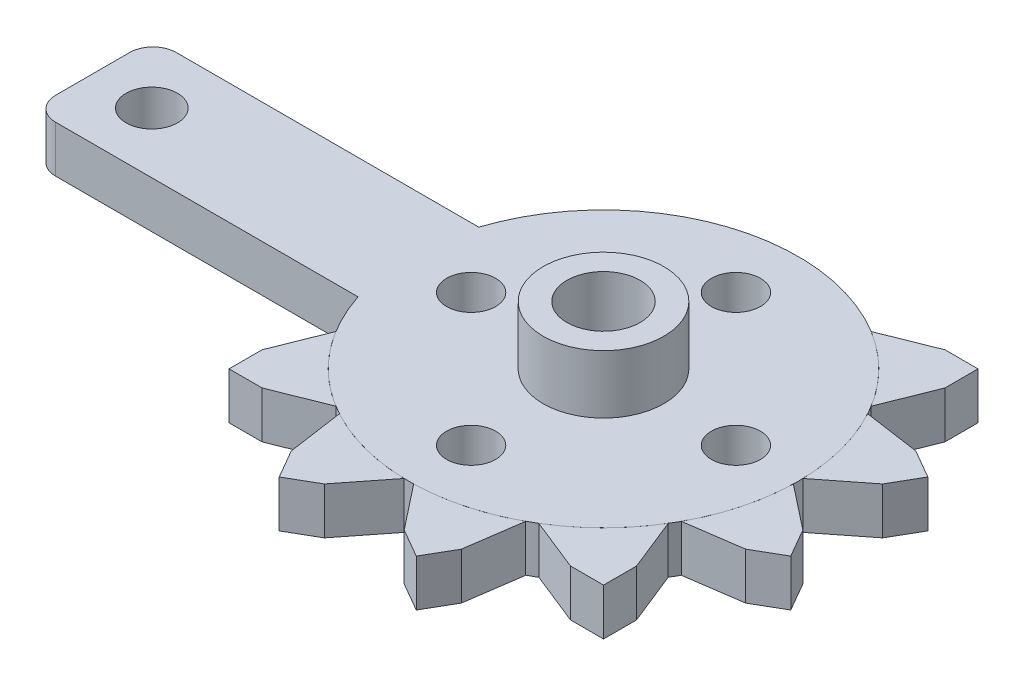
SolidWorks part; units mm, degrees
note: The reader was unsure of these and kept them because the rebuilt part matched: shared geometry of "Sketch1<3>".
ref_plane "Front Plane" through (0, 0, 0) normal (0, 0, 1) x (1, 0, 0)
ref_plane "Top Plane" through (0, 0, 0) normal (0, 1, 0) x (1, 0, 0)
ref_plane "Right Plane" through (0, 0, 0) normal (1, 0, 0) x (0, 0, -1)
sketch "Sketch1" plane through (0, 0, 0) normal (0, 1, 0) x (1, 0, 0)
  line L0 (-3.875, 0) -> (-3.875, 12.8)
  line L1 (-3.875, 12.8) -> (3.875, 12.8)
  line L2 (3.875, 12.8) -> (3.875, 0)
  line L3 (0, 0) -> (0, 8.5)
  line L4 (0, 3.875) -> (12.8, 3.875)
  line L5 (12.8, 3.875) -> (12.8, -3.875)
  line L6 (12.8, -3.875) -> (0, -3.875)
  line L7 (3.875, 0) -> (3.875, -12.8)
  line L8 (3.875, -12.8) -> (-3.875, -12.8)
  line L9 (-3.875, -12.8) -> (-3.875, 0)
  line L10 (0, -3.875) -> (-12.8, -3.875)
  line L11 (-12.8, -3.875) -> (-12.8, 3.875)
  line L12 (-12.8, 3.875) -> (0, 3.875)
  line L13 (-12.8, -3.875) -> (-32.8, -3.875)
  line L14 (-32.8, -3.875) -> (-32.8, 3.875)
  line L15 (-32.8, 3.875) -> (-12.8, 3.875)
  line L16 (0, 0) -> (-29, 0)
  circle A0 centre (0, 0) radius 2.35
  circle A1 centre (0, 0) radius 5.25
  circle A2 centre (0, 0) radius 3.875
  circle A3 centre (0, 8.5) radius 1.575
  circle A4 centre (8.5, 0) radius 1.575
  circle A5 centre (0, -8.5) radius 1.575
  circle A6 centre (-8.5, 0) radius 1.575
  circle A7 centre (0, 0) radius 12.5
  circle A8 centre (-29, 0) radius 1.65
  point P26 (0, 0)
  point P29 (0, 0)
  dimension "D1" = 4.7
  dimension "D2" = 10.5
  dimension "D3" = 7.75
  dimension "D5" = 3.15
  dimension "D9" = 25
  dimension "D13" = 3.3
  dimension "D4" = 8.5
  dimension "D6" = 7.75
  dimension "D10" = 12.8
  dimension "D11" = 20
  dimension "D12" = 29
  dimension "D7" = 4
  dimension "D8" = 4
extrude "Boss-Extrude1" add sketch "Sketch1" along normal blind 3
extrude "Boss-Extrude2" add sketch "Sketch1<3>" along normal blind 6.75
sketch "Sketch1<3>" plane through (0, 0, 0) normal (0, 1, 0) x (1, 0, 0) same geometry as "Sketch1"
sketch "Sketch5" plane through (0, 3, 0) normal (0, 1, 0) x (1, 0, 0)
  line L0 (0, 0) -> (-3.1058, -11.5911)
  line L14 (-0.2081, -12.3676) -> (-6.0036, -10.8147)
  line L17 (0, 0) -> (0, -12.5)
  line L21 (-0.2081, -12.3676) -> (-0.7257, -14.2994)
  line L26 (-6.0036, -10.8147) -> (-6.5212, -12.7465)
  line L29 (-4.3999, -16.4207) -> (-4.0117, -14.9719)
  line L45 (-6.0036, -10.8147) -> (-4.3999, -16.4207)
  line L46 (-4.3999, -16.4207) -> (-0.2081, -12.3676)
  line L47 (-2.5628, -15.3601) -> (-5.4606, -14.5836)
  line L48 (-5.4606, -14.5836) -> (-6.0036, -10.8147)
  line L49 (-2.5628, -15.3601) -> (-0.2081, -12.3676)
  line L50 (-2.5628, -15.3601) -> (-4.3999, -16.4207)
  line L51 (-5.4606, -14.5836) -> (-4.3999, -16.4207)
  arc A11 (-11.8842, -3.875) -> (-11.8842, 3.875) centre (0, 0) ccw construction
  arc A12 (-0.7257, -14.2994) -> (-6.5212, -12.7465) centre (-3.6235, -13.523) cw
  arc M13 (-11.8842, -3.875) -> (-11.8842, 3.875) centre (0, 0) ccw
  dimension "D1" = 15
  dimension "D2" = 12
  dimension "D5" = 3
  dimension "D6" = 6
  dimension "D7" = 2
  dimension "D4" = 1.5
extrude "Boss-Extrude3" add sketch "Sketch5" against normal blind 3 separate body contours L29 L47 L45 | L47 L51 L45 | L48 L47 L45 M13 | L47 L46 L45 M13 | L46 L47 L29 | L50 L47 L46 | L47 L49 L46 M13
pattern_circular "CirPattern3" count 6 every 30 about axis through (0, 0, 0) along (0, 1, 0) of bodies 104
pattern_circular "CirPattern4" count 2 every 30 about axis through (0, 0, 0) along (0, 1, 0) of bodies 104
fillet "Fillet2" radius 1.5 2 edges at (-32.8, 1.5, 3.875) (-32.8, 1.5, -3.875)
